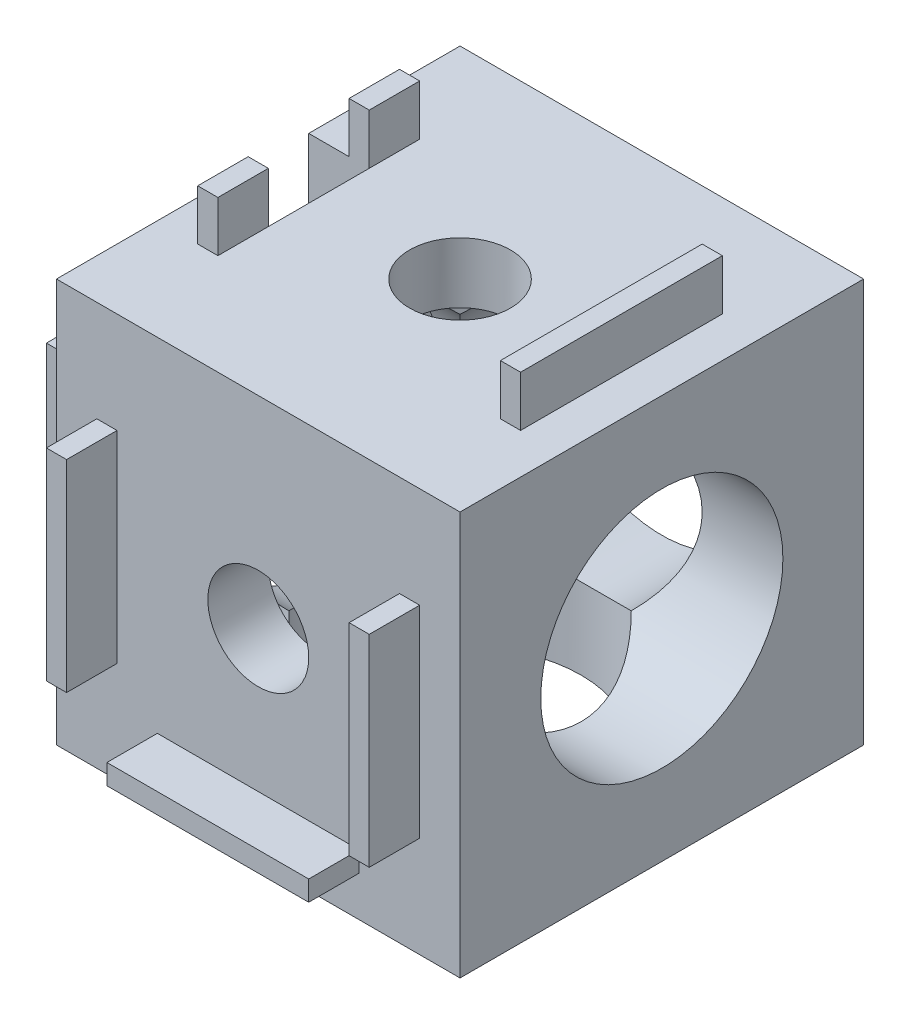
SolidWorks part; units mm, degrees
note: The reader was unsure of these and kept them because the rebuilt part matched: shared geometry of "Sketch2<3>", "Sketch4<3>".
ref_plane "Front Plane" through (0, 0, 0) normal (0, 0, 1) x (1, 0, 0)
ref_plane "Top Plane" through (0, 0, 0) normal (0, 1, 0) x (1, 0, 0)
ref_plane "Right Plane" through (0, 0, 0) normal (1, 0, 0) x (0, 0, -1)
sketch "Sketch1" plane through (0, 0, 0) normal (0, 1, 0) x (1, 0, 0)
  line L0 (0, 7.5) -> (3, 7.5)
  line L1 (0, 0) -> (20, 0)
  line L2 (0, 0) -> (0, 7.5)
  line L3 (0, 20) -> (20, 20)
  line L4 (20, 0) -> (20, 20)
  line L5 (3, 7.5) -> (3, 12.5)
  line L6 (3, 12.5) -> (0, 12.5)
  line L7 (0, 12.5) -> (0, 20)
extrude "Boss-Extrude1" add sketch "Sketch1" along normal blind 20
sketch "Sketch2" plane through (0, 20, 0) normal (0, 1, 0) x (1, 0, 0)
  line L1 (2, 7.5) -> (3, 7.5)
  line L2 (2, 7.5) -> (2, 5)
  line L3 (2, 5) -> (3, 5)
  line L4 (3, 7.5) -> (3, 5)
  line L5 (2, 15) -> (3, 15)
  line L6 (2, 15) -> (2, 12.5)
  line L7 (2, 12.5) -> (3, 12.5)
  line L8 (3, 15) -> (3, 12.5)
  line L9 (17, 15) -> (18, 15)
  line L10 (17, 15) -> (17, 5)
  line L11 (17, 5) -> (18, 5)
  line L12 (18, 15) -> (18, 5)
  circle A0 centre (10, 10) radius 2.5
extrude "Boss-Extrude2" add sketch "Sketch2" along normal blind 2.5 contours L4 L2 L3 | L8 L5 L6 A0 | L12 L9 L10 L11
extrude "Cut-Extrude1" cut sketch "Sketch2<3>" against normal through all contours A0
sketch "Sketch2<3>" plane through (0, 20, 0) normal (0, 1, 0) x (1, 0, 0) same geometry as "Sketch2"
sketch "Sketch3" plane through (0, 0, 0) normal (-1, 0, 0) x (0, 0, 1)
  line L1 (-2, 15) -> (-3, 15)
  line L2 (-2, 15) -> (-2, 5)
  line L3 (-2, 5) -> (-3, 5)
  line L4 (-3, 15) -> (-3, 5)
  line L5 (-18, 15) -> (-17, 15)
  line L6 (-18, 15) -> (-18, 5)
  line L7 (-18, 5) -> (-17, 5)
  line L8 (-17, 15) -> (-17, 5)
extrude "Boss-Extrude3" add sketch "Sketch3" along normal blind 2.5
sketch "Sketch4" plane through (0, 0, 0) normal (0, 0, -1) x (-1, 0, 0)
  line L1 (-18, 15) -> (-17, 15)
  line L2 (-18, 15) -> (-18, 5)
  line L3 (-18, 5) -> (-17, 5)
  line L4 (-17, 15) -> (-17, 5)
  line L5 (-2, 15) -> (-3, 15)
  line L6 (-2, 15) -> (-2, 5)
  line L7 (-2, 5) -> (-3, 5)
  line L8 (-3, 15) -> (-3, 5)
  line L9 (-15, 3) -> (-5, 3)
  line L10 (-15, 3) -> (-15, 2)
  line L11 (-15, 2) -> (-5, 2)
  line L12 (-5, 3) -> (-5, 2)
  circle A0 centre (-10, 10) radius 2.5
extrude "Boss-Extrude4" add sketch "Sketch4" against normal blind 2.5 contours L1 L4 L3 L2 | L6 L7 L8 L5 | L11 L12 L9 L10
extrude "Cut-Extrude2" cut sketch "Sketch4<3>" along normal through all contours A0
sketch "Sketch4<3>" plane through (0, 0, 0) normal (0, 0, -1) x (-1, 0, 0) same geometry as "Sketch4"
sketch "Sketch5" plane through (20, 0, 0) normal (1, 0, 0) x (0, 0, -1)
  circle A0 centre (10, 10) radius 6
extrude "Cut-Extrude3" cut sketch "Sketch5" against normal blind 17
sketch "Sketch6" plane through (0, 0, -20) normal (0, 0, 1) x (1, 0, 0)
  circle A0 centre (10, 10) radius 6
extrude "Cut-Extrude4" cut sketch "Sketch6" along normal blind 17
sketch "Sketch7" plane through (0, 0, 0) normal (0, -1, 0) x (1, 0, 0)
  circle A0 centre (10, -10) radius 6
extrude "Cut-Extrude5" cut sketch "Sketch7" against normal blind 17
